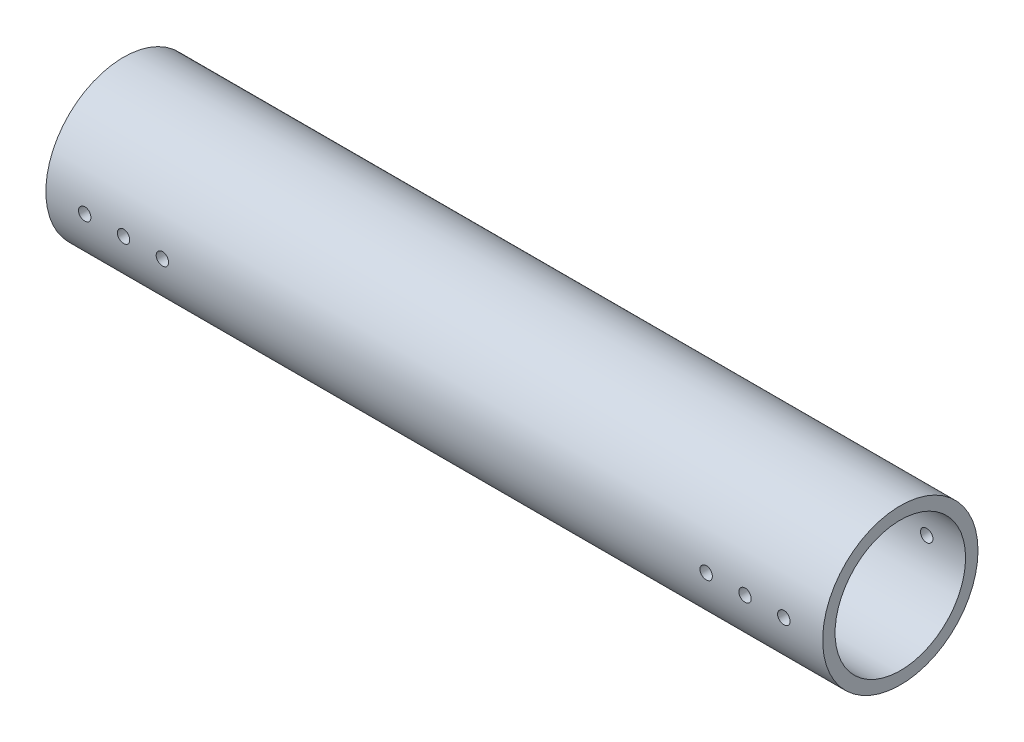
SolidWorks part; units mm, degrees
material "Zoltek Panex 33"
ref_plane "Спереди" through (0, 0, 0) normal (0, 0, 1) x (1, 0, 0)
ref_plane "Сверху" through (0, 0, 0) normal (0, 1, 0) x (1, 0, 0)
ref_plane "Справа" through (0, 0, 0) normal (1, 0, 0) x (0, 0, -1)
other "Configuration Table"
sketch "Эскиз2" plane through (0, 0, 0) normal (1, 0, 0) x (0, 0, -1)
  circle A0 centre (0, 0) radius 25
  circle A1 centre (0, 0) radius 21
  dimension "D1" = 50
  dimension "D2" = 42
extrude "Бобышка-Вытянуть2" add sketch "Эскиз2" along normal blind 250
ref_plane "Плоскость1" through (0, 0, 25) normal (0, 0, 1) x (1, 0, 0)
sketch "Эскиз4" plane through (0, 0, 25) normal (0, 0, 1) x (1, 0, 0)
  line L0 (0, -25) -> (250, -25) construction
  line L1 (250, -25) -> (250, 25) construction
  circle A0 centre (12.5, 0) radius 2
  circle A1 centre (237.5, 0) radius 2
  circle A2 centre (25, 0) radius 2
  circle A3 centre (37.5, 0) radius 2
  circle A4 centre (225, 0) radius 2
  circle A5 centre (212.5, 0) radius 2
  dimension "D1" = 4
  dimension "D4" = 4
  dimension "D6" = 4
  dimension "D8" = 4
  dimension "D10" = 4
  dimension "D11" = 4
  dimension "D2" = 12.5
  dimension "D3" = 25
  dimension "D5" = 12.5
  dimension "D7" = 12.5
  dimension "D9" = 12.5
  dimension "15" = 12.5
  dimension "D12" = 12.5
extrude "Вырез-Вытянуть2" cut sketch "Эскиз4" against normal through all and the other way blind 10 contours A0 | A1 | A2 | A3 | A5 | A4
equation "\"Diameter\"= 50мм"
equation "\"D1@Эскиз2\"= \"Diameter\""
equation "\"Length\"= 250мм"
equation "\"Thickness\"= 4мм"
equation "\"D1@Бобышка-Вытянуть2\"= \"Length\""
equation "\"D2@Эскиз2\" = \"Diameter\" - \"Thickness\" * 2"
equation "\"D4@Эскиз4\"=\"D1@Эскиз4\""
equation "\"D5@Эскиз4\"=\"D2@Эскиз4\""
equation "\"D3@Эскиз4\"=\"Diameter\"/2"
equation "\"D6@Эскиз4\"=\"D1@Эскиз4\""
equation "\"D8@Эскиз4\"=\"D6@Эскиз4\""
equation "\"D10@Эскиз4\"=\"D4@Эскиз4\""
equation "\"D11@Эскиз4\"=\"D4@Эскиз4\""
equation "\"D9@Эскиз4\"=\"D7@Эскиз4\""
